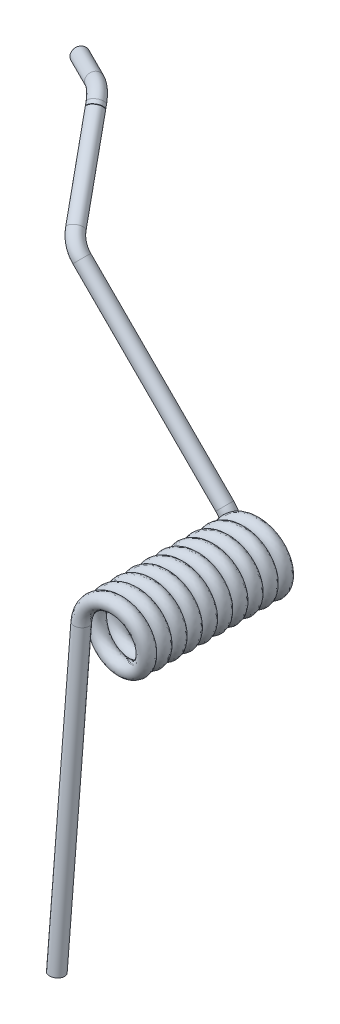
SolidWorks part; units mm, degrees
material "Brass"
ref_plane "Front Plane" through (0, 0, 0) normal (0, 0, 1) x (1, 0, 0)
ref_plane "Top Plane" through (0, 0, 0) normal (0, 1, 0) x (1, 0, 0)
ref_plane "Right Plane" through (0, 0, 0) normal (1, 0, 0) x (0, 0, -1)
sketch "Sketch2" plane through (0, 0, 0) normal (0, 0, 1) x (1, 0, 0)
  circle A0 centre (0, 0) radius 3.4417
  dimension "D1" = 6.8834
curve "Helix/Spiral1" pitch 1.8161 height 18.161 radius 3.4417 centre (0, 0, 0) axis (0, 0, 1) start towards (-1, 0, 0)
sweep "Sweep1" add path "Helix/Spiral1" circular profile diameter 1.7526 parameters "D3"=1.7526
ref_plane "Plane3" through (-3.4417, 0, 0) normal (1, 0, 0) x (0, 0, -1)
sketch "Sketch19" plane through (-3.4417, 0, 0) normal (1, 0, 0) x (0, 0, -1)
  line L0 (-18.161, 0) -> (-21.0838, -34.8025)
  line L1 (-19.0342, 0.0733) -> (-17.2878, -0.0733) construction
  spline S0 degree 3 poles (0, 0) (-0.0376, -0.4476) (-0.1136, -1.3527) (-0.227, -2.4967) (-0.3405, -3.2626) (-0.454, -3.5313) (-0.5675, -3.2625) (-0.681, -2.497) (-0.8324, -0.9695) (-0.9837, 0.9695) (-1.1351, 2.497) (-1.2486, 3.2625) (-1.3621, 3.5313) (-1.4756, 3.2625) (-1.5891, 2.497) (-1.7404, 0.9695) (-1.8918, -0.9695) (-2.0431, -2.497) (-2.1566, -3.2625) (-2.2701, -3.5313) (-2.3836, -3.2625) (-2.4971, -2.497) (-2.6485, -0.9695) (-2.7998, 0.9695) (-2.9512, 2.497) (-3.0647, 3.2625) (-3.1782, 3.5313) (-3.2917, 3.2625) (-3.4052, 2.497) (-3.5565, 0.9695) (-3.7079, -0.9695) (-3.8592, -2.497) (-3.9727, -3.2625) (-4.0862, -3.5313) (-4.1997, -3.2625) (-4.3132, -2.497) (-4.4646, -0.9695) (-4.6159, 0.9695) (-4.7673, 2.497) (-4.8808, 3.2625) (-4.9943, 3.5313) (-5.1078, 3.2625) (-5.2213, 2.497) (-5.3726, 0.9695) (-5.524, -0.9695) (-5.6753, -2.497) (-5.7888, -3.2625) (-5.9023, -3.5313) (-6.0158, -3.2625) (-6.1293, -2.497) (-6.2807, -0.9695) (-6.432, 0.9695) (-6.5834, 2.497) (-6.6969, 3.2625) (-6.8104, 3.5313) (-6.9239, 3.2625) (-7.0374, 2.497) (-7.1887, 0.9695) (-7.3401, -0.9695) (-7.4914, -2.497) (-7.6049, -3.2625) (-7.7184, -3.5313) (-7.8319, -3.2625) (-7.9454, -2.497) (-8.0968, -0.9695) (-8.2481, 0.9695) (-8.3995, 2.497) (-8.513, 3.2625) (-8.6265, 3.5313) (-8.74, 3.2625) (-8.8535, 2.497) (-9.0048, 0.9695) (-9.1562, -0.9695) (-9.3075, -2.497) (-9.421, -3.2625) (-9.5345, -3.5313) (-9.648, -3.2625) (-9.7615, -2.497) (-9.9129, -0.9695) (-10.0642, 0.9695) (-10.2156, 2.497) (-10.3291, 3.2625) (-10.4426, 3.5313) (-10.5561, 3.2625) (-10.6696, 2.497) (-10.8209, 0.9695) (-10.9723, -0.9695) (-11.1236, -2.497) (-11.2371, -3.2625) (-11.3506, -3.5313) (-11.4641, -3.2625) (-11.5776, -2.497) (-11.729, -0.9695) (-11.8803, 0.9695) (-12.0317, 2.497) (-12.1452, 3.2625) (-12.2587, 3.5313) (-12.3722, 3.2625) (-12.4857, 2.497) (-12.637, 0.9695) (-12.7884, -0.9695) (-12.9397, -2.497) (-13.0532, -3.2625) (-13.1667, -3.5313) (-13.2802, -3.2625) (-13.3937, -2.497) (-13.5451, -0.9695) (-13.6964, 0.9695) (-13.8478, 2.497) (-13.9613, 3.2625) (-14.0748, 3.5313) (-14.1883, 3.2625) (-14.3018, 2.497) (-14.4531, 0.9695) (-14.6045, -0.9695) (-14.7558, -2.497) (-14.8693, -3.2625) (-14.9828, -3.5313) (-15.0963, -3.2625) (-15.2098, -2.497) (-15.3612, -0.9695) (-15.5125, 0.9695) (-15.6639, 2.497) (-15.7774, 3.2625) (-15.8909, 3.5313) (-16.0044, 3.2625) (-16.1179, 2.497) (-16.2692, 0.9695) (-16.4206, -0.9695) (-16.5719, -2.497) (-16.6854, -3.2625) (-16.7989, -3.5313) (-16.9124, -3.2625) (-17.0259, -2.497) (-17.1773, -0.9695) (-17.3286, 0.9695) (-17.48, 2.497) (-17.5935, 3.2625) (-17.707, 3.5313) (-17.8205, 3.2626) (-17.934, 2.4967) (-18.0474, 1.3527) (-18.1234, 0.4476) (-18.161, 0) knots 0 0 0 0 0.00625 0.0125 0.01875 0.025 0.03125 0.0375 0.04375 0.05625 0.0625 0.06875 0.075 0.08125 0.0875 0.09375 0.10625 0.1125 0.11875 0.125 0.13125 0.1375 0.14375 0.15625 0.1625 0.16875 0.175 0.18125 0.1875 0.19375 0.20625 0.2125 0.21875 0.225 0.23125 0.2375 0.24375 0.25625 0.2625 0.26875 0.275 0.28125 0.2875 0.29375 0.30625 0.3125 0.31875 0.325 0.33125 0.3375 0.34375 0.35625 0.3625 0.36875 0.375 0.38125 0.3875 0.39375 0.40625 0.4125 0.41875 0.425 0.43125 0.4375 0.44375 0.45625 0.4625 0.46875 0.475 0.48125 0.4875 0.49375 0.50625 0.5125 0.51875 0.525 0.53125 0.5375 0.54375 0.55625 0.5625 0.56875 0.575 0.58125 0.5875 0.59375 0.60625 0.6125 0.61875 0.625 0.63125 0.6375 0.64375 0.65625 0.6625 0.66875 0.675 0.68125 0.6875 0.69375 0.70625 0.7125 0.71875 0.725 0.73125 0.7375 0.74375 0.75625 0.7625 0.76875 0.775 0.78125 0.7875 0.79375 0.80625 0.8125 0.81875 0.825 0.83125 0.8375 0.84375 0.85625 0.8625 0.86875 0.875 0.88125 0.8875 0.89375 0.90625 0.9125 0.91875 0.925 0.93125 0.9375 0.94375 0.95625 0.9625 0.96875 0.975 0.98125 0.9875 0.99375 1 1 1 1 construction
  dimension "D1" = 34.925
sweep "Sweep3" add path "Sketch19" circular profile diameter 1.7526 parameters "D3"=1.7526
ref_plane "Plane6" through (0, 0, 0) normal (0, 0, 1) x (1, 0, 0)
sketch "Sketch60" plane through (0, 0, 0) normal (0, 0, 1) x (1, 0, 0)
  line L0 (-3.4417, -0.0733) -> (-3.4417, 0.0251)
  line L1 (-4.4498, 2.4587) -> (-21.4022, 19.4112)
  arc A0 (-3.4417, 0.0251) -> (-4.4498, 2.4587) centre (-6.8834, 0.0251) ccw
  ellipse E0 centre (-3.4417, 0) end of major axis (-4.318, 0) minor radius 0.0733 construction
  point P11 (-3.4417, 1.4507)
  dimension "D4" = 3.4417
  dimension "D1" = 1.524
  dimension "D2" = 135
  dimension "D3" = 25.4
sweep "Sweep7" add path "Sketch60" circular profile diameter 1.7526 parameters "D3"=1.7526
ref_plane "Plane7" through (-0.9955, -0.9955, 0) normal (0.7071, 0.7071, 0) x (-0.7071, 0.7071, 0)
sketch "Sketch69" plane through (-0.9955, -0.9955, 0) normal (0.7071, 0.7071, 0) x (-0.7071, 0.7071, 0)
  line L0 (28.8594, 0) -> (29.0499, 0)
  line L1 (4.885, 0) -> (28.8594, 0) construction
  line L2 (31.4836, -1.0081) -> (39.4558, -8.9803)
  arc A0 (29.0499, 0) -> (31.4836, -1.0081) centre (29.0499, -3.4417) cw
  point P8 (30.4755, 0)
  dimension "D3" = 3.4417
  dimension "D1" = 135
  dimension "D2" = 12.7
  dimension "D4" = 0.1905
sweep "Sweep8" add path "Sketch69" circular profile diameter 1.7526 parameters "D3"=1.7526
ref_plane "Plane8" through (-10.7747, 10.7747, 15.2378) normal (0.5, -0.5, -0.7071) x (-0.5, 0.5, -0.7071)
sketch "Sketch76" plane through (-10.7747, 10.7747, 15.2378) normal (0.5, -0.5, -0.7071) x (-0.5, 0.5, -0.7071)
  line L0 (34.2944, -1.4079) -> (34.7738, -1.4079)
  line L1 (22.975, -1.4079) -> (34.2494, -1.4079) construction
  line L2 (37.2074, -2.4159) -> (40.6895, -5.898)
  arc A0 (34.7738, -1.4079) -> (37.2074, -2.4159) centre (34.7738, -4.8496) cw
  point P7 (36.1994, -1.4079)
  dimension "D4" = 3.4417
  dimension "D1" = 135
  dimension "D2" = 6.35
  dimension "D3" = 1.905
sweep "Sweep9" add path "Sketch76" circular profile diameter 1.7526 parameters "D3"=1.7526
